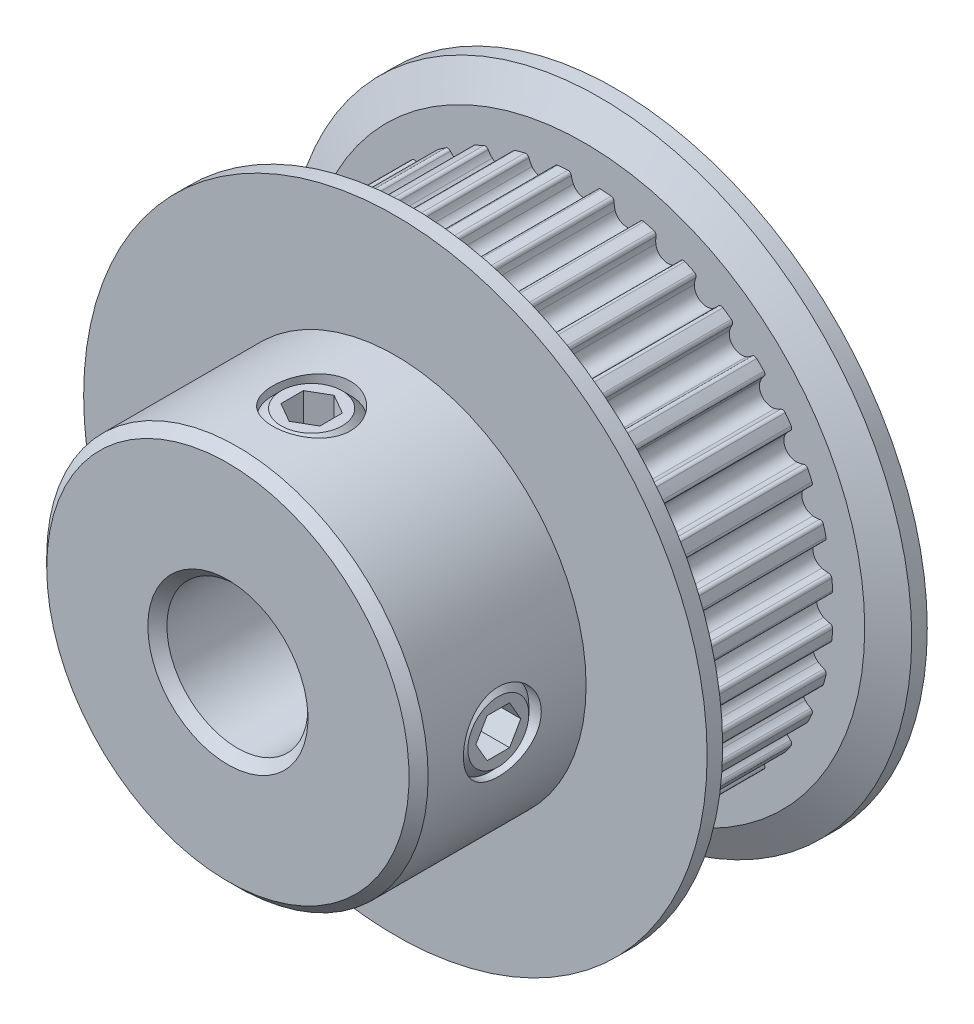
SolidWorks part; units mm, degrees
ref_plane "Front Plane" through (0, 0, 0) normal (0, 0, 1) x (1, 0, 0)
ref_plane "Top Plane" through (0, 0, 0) normal (0, 1, 0) x (1, 0, 0)
ref_plane "Right Plane" through (0, 0, 0) normal (1, 0, 0) x (0, 0, -1)
sketch "Sketch1" plane through (0, 0, 0) normal (0, 0, 1) x (1, 0, 0)
  line L1 (-1.8459, 10.4515) -> (1.8459, 10.4515) construction
  line L4 (0, 0) -> (0, 10.4515) construction
  line L5 (0, 10.4515) -> (0, 14.6076) construction
  line L6 (0, 11.4555) -> (1.9924, 11.2809) construction
  line L7 (1.9924, 11.2809) -> (2.8218, 11.1344) construction
  line L8 (1.9924, 11.2809) -> (1.8459, 10.4515) construction
  line L9 (-1.9924, 11.2809) -> (-1.8459, 10.4515) construction
  line L10 (-1.9482, 11.0308) -> (-2.4785, 14.0335)
  line L11 (-2.4785, 14.0335) -> (2.4785, 14.0335)
  line L12 (2.4785, 14.0335) -> (1.9482, 11.0308)
  circle A0 centre (0, 0) radius 11.4555 construction
  circle A1 centre (0, 0) radius 14.0335 construction
  circle A2 centre (0, 0) radius 11.2015 construction
  arc A3 (-0.4989, 10.7633) -> (0.4989, 10.7633) centre (0, 11.0065) ccw
  arc A4 (-0.4989, 10.7633) -> (-0.5884, 11.0497) centre (0.4, 11.2015) cw
  arc A5 (-1.9482, 11.0308) -> (-0.7467, 11.1766) centre (0, 0) cw
  arc A6 (-0.5884, 11.0497) -> (-0.7467, 11.1766) centre (-0.7367, 11.0269) ccw
  arc A7 (1.9482, 11.0308) -> (0.7467, 11.1766) centre (0, 0) ccw
  arc A8 (0.5884, 11.0497) -> (0.7467, 11.1766) centre (0.7367, 11.0269) cw
  arc A9 (0.4989, 10.7633) -> (0.5884, 11.0497) centre (-0.4, 11.2015) ccw
  point P6 (0, 20.9083)
  point P11 (0, 11.4555)
  point P13 (0, 14.0335)
  point P14 (0, 11.2015)
  dimension "D1" = 6.3008
  dimension "D2" = 3.1521
sketch "Sketch2" plane through (0, 0, 0) normal (1, 0, 0) x (0, 0, -1)
  line L0 (-8.7249, 3.175) -> (8.7249, 3.175)
  line L1 (-8.7249, 3.175) -> (-8.7249, 8.585)
  line L2 (-8.7249, 8.585) -> (-1.1851, 8.585)
  line L3 (-1.1851, 8.585) -> (-1.1851, 14.0335)
  line L4 (-1.1851, 14.0335) -> (0.2149, 14.0335) construction
  line L5 (0.2149, 14.0335) -> (0.2149, 11.2015) construction
  line L6 (0.2149, 11.2015) -> (7.3249, 11.2015)
  line L7 (7.3249, 11.2015) -> (7.3249, 14.0335) construction
  line L8 (7.3249, 14.0335) -> (8.7249, 14.0335) construction
  line L9 (8.7249, 14.0335) -> (8.7249, 3.175)
  line L10 (-8.7249, 0) -> (8.7249, 0) construction
  line L11 (8.0249, 14.0335) -> (7.3249, 12.6175)
  line L12 (0.2149, 12.6175) -> (-0.4851, 14.0335)
  line L13 (-1.1851, 14.0335) -> (-0.4851, 14.0335)
  line L14 (0.2149, 12.6175) -> (0.2149, 11.2015)
  line L15 (7.3249, 11.2015) -> (7.3249, 12.6175)
  line L16 (8.0249, 14.0335) -> (8.7249, 14.0335)
  arc A0 (0.2149, 12.6175) -> (-0.4851, 14.0335) centre (-1.5673, 12.6175) ccw construction
  arc A1 (7.3249, 12.6175) -> (8.0249, 14.0335) centre (9.1071, 12.6175) cw construction
  point P12 (0.2149, 12.6175)
  point P14 (-0.4851, 14.0335)
  point P20 (7.3249, 12.6175)
  point P21 (8.0249, 14.0335)
  point P25 (7.3249, 0)
  point P26 (0.2149, 0)
revolve "Revolve1" add sketch "Sketch2" angle 360 mid plane about L10
sketch "Sketch3" plane through (0, 0, 0) normal (0, 0, 1) x (1, 0, 0)
  line L6 (2.4785, 14.0335) -> (-2.4785, 14.0335)
  line L7 (1.9482, 11.0308) -> (2.4785, 14.0335)
  line L8 (-2.4785, 14.0335) -> (-1.9482, 11.0308)
  line L9 (2.4785, 14.0335) -> (-2.4785, 14.0335)
  line L10 (1.9482, 11.0308) -> (2.4785, 14.0335)
  line L11 (-2.4785, 14.0335) -> (-1.9482, 11.0308)
  arc A8 (1.9482, 11.0308) -> (0.7467, 11.1766) centre (0, 0) ccw
  arc A9 (0.7467, 11.1766) -> (0.5884, 11.0497) centre (0.7367, 11.0269) ccw
  arc A10 (0.4989, 10.7633) -> (0.5884, 11.0497) centre (-0.4, 11.2015) ccw
  arc A11 (-0.4989, 10.7633) -> (0.4989, 10.7633) centre (0, 11.0065) ccw
  arc A12 (-0.5884, 11.0497) -> (-0.4989, 10.7633) centre (0.4, 11.2015) ccw
  arc A13 (-0.5884, 11.0497) -> (-0.7467, 11.1766) centre (-0.7367, 11.0269) ccw
  arc A14 (-0.7467, 11.1766) -> (-1.9482, 11.0308) centre (0, 0) ccw
  arc A15 (1.9482, 11.0308) -> (0.7467, 11.1766) centre (0, 0) ccw
  arc A16 (0.7467, 11.1766) -> (0.5884, 11.0497) centre (0.7367, 11.0269) ccw
  arc A17 (0.4989, 10.7633) -> (0.5884, 11.0497) centre (-0.4, 11.2015) ccw
  arc A18 (-0.4989, 10.7633) -> (0.4989, 10.7633) centre (0, 11.0065) ccw
  arc A19 (-0.5884, 11.0497) -> (-0.4989, 10.7633) centre (0.4, 11.2015) ccw
  arc A20 (-0.5884, 11.0497) -> (-0.7467, 11.1766) centre (-0.7367, 11.0269) ccw
  arc A21 (-0.7467, 11.1766) -> (-1.9482, 11.0308) centre (0, 0) ccw
  dimension "D1" = 0
extrude "Cut-Extrude1" cut sketch "Sketch3" against normal up to vertex (7.3249 mm away) from vertex up to point (0, 11.2015, -7.3249) starting at point (0, 11.2015, -0.2149)
pattern_circular "CirPattern1" count 36 over 360 about axis through (0, 0, 8.7249) along (0, 0, 1) of "Cut-Extrude1"
sketch "Sketch4" plane through (0, 0, 0) normal (1, 0, 0) x (0, -1, 0)
  line L0 (0, -1.1851) -> (0, -8.7249) construction
  line L1 (-8.585, -1.1851) -> (8.585, -1.1851) construction
  line L2 (-8.585, -8.7249) -> (8.585, -8.7249) construction
  circle A0 centre (0, -4.955) radius 1.7526
extrude "Cut-Extrude2" cut sketch "Sketch4" along normal through all
ref_plane "Plane1" through (0, 0, 4.955) normal (0, 0, 1) x (1, 0, 0)
sketch "Sketch5" plane through (0, 0, 4.955) normal (0, 0, 1) x (1, 0, 0)
  line L0 (0, 0.1664) -> (0, 8.585) construction
  line L1 (3.175, -1.3716) -> (3.175, 0)
  line L2 (3.556, -1.7526) -> (8.0232, -1.7526)
  line L3 (3.175, 0) -> (8.585, 0) construction
  line L4 (3.175, 0) -> (8.4042, 0)
  line L5 (8.4042, 0) -> (8.4042, -1.3716)
  line L6 (3.556, -1.7526) -> (3.175, -1.3716)
  line L7 (8.4042, -1.3716) -> (8.0232, -1.7526)
  circle A0 centre (0, 0) radius 8.585 construction
  circle A1 centre (0, 0) radius 3.175 construction
  point P2 (3.175, -1.7526)
  point P11 (8.4042, -1.7526)
revolve "Revolve2" add sketch "Sketch5" angle 360 mid plane about L4
sketch "Sketch6" plane through (8.4042, 5.3841, 0) normal (-1, 0, 0) x (0, -1, 0)
  line L1 (5.3841, 5.9669) -> (4.5078, 5.4609)
  line L2 (4.5078, 5.4609) -> (4.5078, 4.4491)
  line L3 (4.5078, 4.4491) -> (5.3841, 3.9431)
  line L4 (5.3841, 3.9431) -> (6.2604, 4.4491)
  line L5 (6.2604, 4.4491) -> (6.2604, 5.4609)
  line L6 (6.2604, 5.4609) -> (5.3841, 5.9669)
  circle A0 centre (5.3841, 4.955) radius 0.8763 construction
  dimension "D1" = 1.7526
extrude "Cut-Extrude3" cut sketch "Sketch6" along normal blind 1.3144
pattern_circular "CirPattern2" count 2 over 90 about axis through (0, 0, 8.7249) along (0, 0, 1) of "Cut-Extrude2", "Revolve2", "Cut-Extrude3"
chamfer "Chamfer1" distance 0.4293 angle 45 2 edges at (3.175, 0, 8.7249) (8.585, 0, 8.7249)
ref_axis "Center Axis 1" through (0, 0, -8.7249) along (0, 0, 1)
ref_plane "Contact Plane 1" through (0, 0, 8.7249) normal (0, 0, 1) x (1, 0, 0)
ref_plane "Contact Plane 2" through (0, 0, -8.7249) normal (0, 0, -1) x (-1, 0, 0)
equation "\"D2@Sketch1\" = \"D1@Sketch1\"/2"
equation "\"D1@Sketch6\" = \"Set Screw@Sketch4\" / 2"
equation "\"D1@Cut-Extrude3\" = \"D1@Sketch6\"*.75"
equation "\"D1@Chamfer1\"=\"Hub Dia@Sketch2\"*.025"
